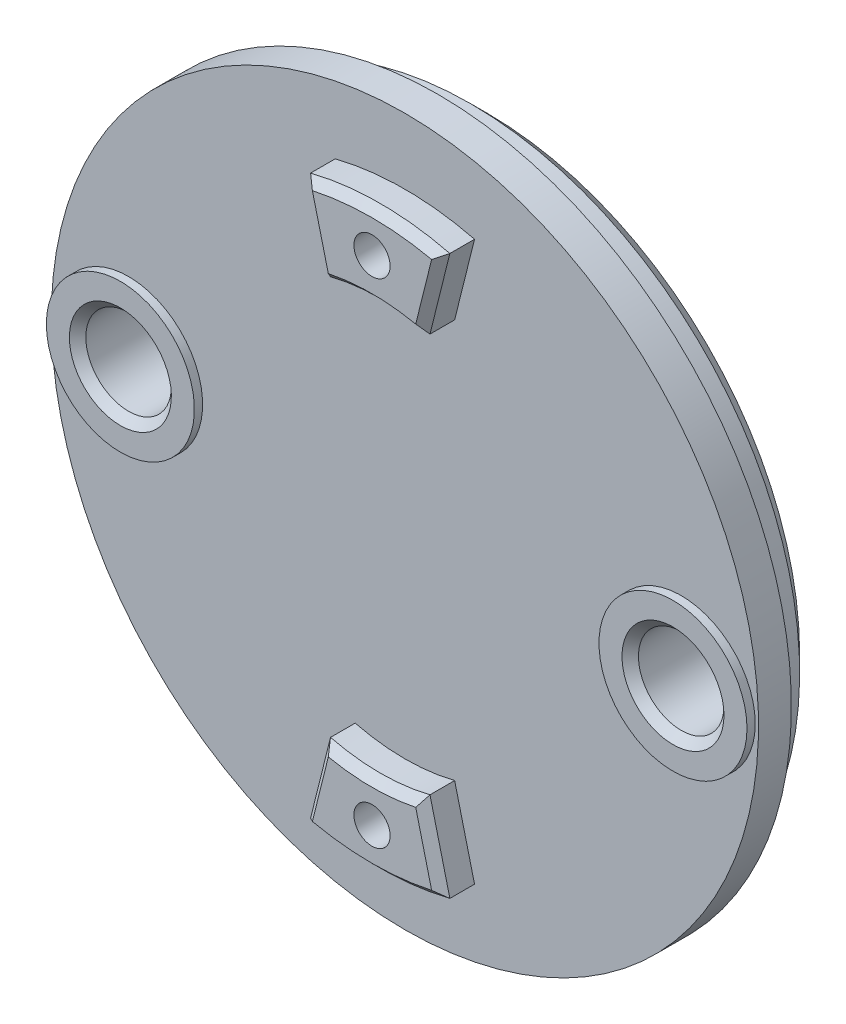
SolidWorks part; units mm, degrees
ref_plane "Front Plane" through (0, 0, 0) normal (0, 0, 1) x (1, 0, 0)
ref_plane "Top Plane" through (0, 0, 0) normal (0, 1, 0) x (1, 0, 0)
ref_plane "Right Plane" through (0, 0, 0) normal (1, 0, 0) x (0, 0, -1)
sketch "Sketch1" plane through (0, 0, 0) normal (1, 0, 0) x (0, 0, -1)
  line L0 (0, 0) -> (0, 21.5)
  line L1 (0, 21.5) -> (2, 21.5)
  line L2 (2, 21.5) -> (2, 20)
  line L3 (2, 20) -> (5, 20)
  line L4 (5, 20) -> (5, 0)
  line L5 (5, 0) -> (0, 0)
  dimension "D1" = 21.5
  dimension "D2" = 20
  dimension "D3" = 3
  dimension "D4" = 5
revolve "Revolve1" add sketch "Sketch1" angle 360 about L5
sketch "Sketch2" plane through (0, 0, 0) normal (0, 0, 1) x (1, 0, 0)
  line L0 (0, 0) -> (28.634, 0) construction
  circle A0 centre (16.8, 0) radius 2.6
  dimension "D2" = 5.2
  dimension "D3" = 16.8
extrude "Cut-Extrude1" cut sketch "Sketch2" against normal blind 10 contours A0
sketch "Sketch3" plane through (0, 0, 0) normal (0, 0, 1) x (1, 0, 0)
  line L0 (0, 0) -> (0, 26.9366) construction
  circle A0 centre (0, 15) radius 1.1
  dimension "D1" = 2.2
  dimension "D2" = 15
extrude "Cut-Extrude2" cut sketch "Sketch3" against normal blind 10
pattern_circular "CirPattern2" count 2 over 360 about axis through (0, 0, 0) along (0, 0, 1) of "Cut-Extrude2"
chamfer "Chamfer2" distance 1 angle 45 1 edges at (0, 20, -5)
sketch "Sketch4" plane through (0, 0, -5) normal (0, 0, -1) x (-1, 0, 0)
  line L0 (0, 0) -> (-17.0399, 17.0399) construction
  line L1 (0, 0) -> (-33.1335, 0) construction
  line L3 (-11.4285, 13.6738) -> (-13.6738, 11.4285)
  line L4 (-13.6738, 11.4285) -> (-12.852, 8.3612)
  line L5 (-12.852, 8.3612) -> (-9.7847, 7.5394)
  line L6 (-9.7847, 7.5394) -> (-7.5394, 9.7847)
  line L7 (-7.5394, 9.7847) -> (-8.3612, 12.852)
  line L8 (-8.3612, 12.852) -> (-11.4285, 13.6738)
  circle A0 centre (-10.6066, 10.6066) radius 1.65
  circle A1 centre (-10.6066, 10.6066) radius 2.75 construction
  dimension "D3" = 3.3
  dimension "D1" = 15
  dimension "D2" = 5.5
extrude "Cut-Extrude3" cut sketch "Sketch4" against normal blind 2.5
sketch "Sketch7" plane through (0, 0, -5) normal (0, 0, -1) x (-1, 0, 0)
  circle A1 centre (-10.6066, 10.6066) radius 1.65
  circle A2 centre (-10.6066, 10.6066) radius 1.65
  dimension "D1" = 0
extrude "Cut-Extrude4" cut sketch "Sketch7" against normal blind 4.5
pattern_circular "CirPattern3" count 4 over 360 about axis through (0, 0, 0) along (0, 0, 1) of "Cut-Extrude4", "Cut-Extrude3"
sketch "Sketch8" plane through (0, 0, 0) normal (0, 0, 1) x (1, 0, 0)
  line L0 (0, 0) -> (-5.8396, -23.4212)
  line L1 (0, 0) -> (0, -15)
  line L2 (0, 0) -> (5.8396, -23.4212)
  arc A1 (3.024, -12.1287) -> (-3.024, -12.1287) centre (0, 0) cw
  arc A2 (4.2336, -16.9802) -> (-4.2336, -16.9802) centre (0, 0) cw
  dimension "D3" = 12.5
  dimension "D4" = 17.5
  dimension "D1" = 28
  dimension "D2" = 14
extrude "Boss-Extrude1" add sketch "Sketch8" along normal blind 2
chamfer "Chamfer3" distance 0.5 angle 45 4 edges at (3.6288, -14.5544, 2) (0, -12.5, 2) (-3.6288, -14.5544, 2) (0, -17.5, 2)
pattern_circular "CirPattern4" count 2 over 360 about axis through (0, 0, 0) along (0, 0, 1) of "Chamfer3", "Boss-Extrude1"
sketch "Sketch9" plane through (0, 0, 0) normal (0, 0, 1) x (1, 0, 0)
  circle A0 centre (16.8, 0) radius 2.6 construction
  circle A1 centre (16.8, 0) radius 2.6
  circle A2 centre (16.8, 0) radius 4.5
  dimension "D1" = 9
extrude "Boss-Extrude2" add sketch "Sketch9" along normal blind 0.5
chamfer "Chamfer4" distance 0.5 angle 45 1 edges at (19.4, 0, 0.5)
pattern_circular "CirPattern5" count 2 over 360 about axis through (0, 0, 0) along (0, 0, 1) of "Chamfer4", "Boss-Extrude2", "Cut-Extrude1"
